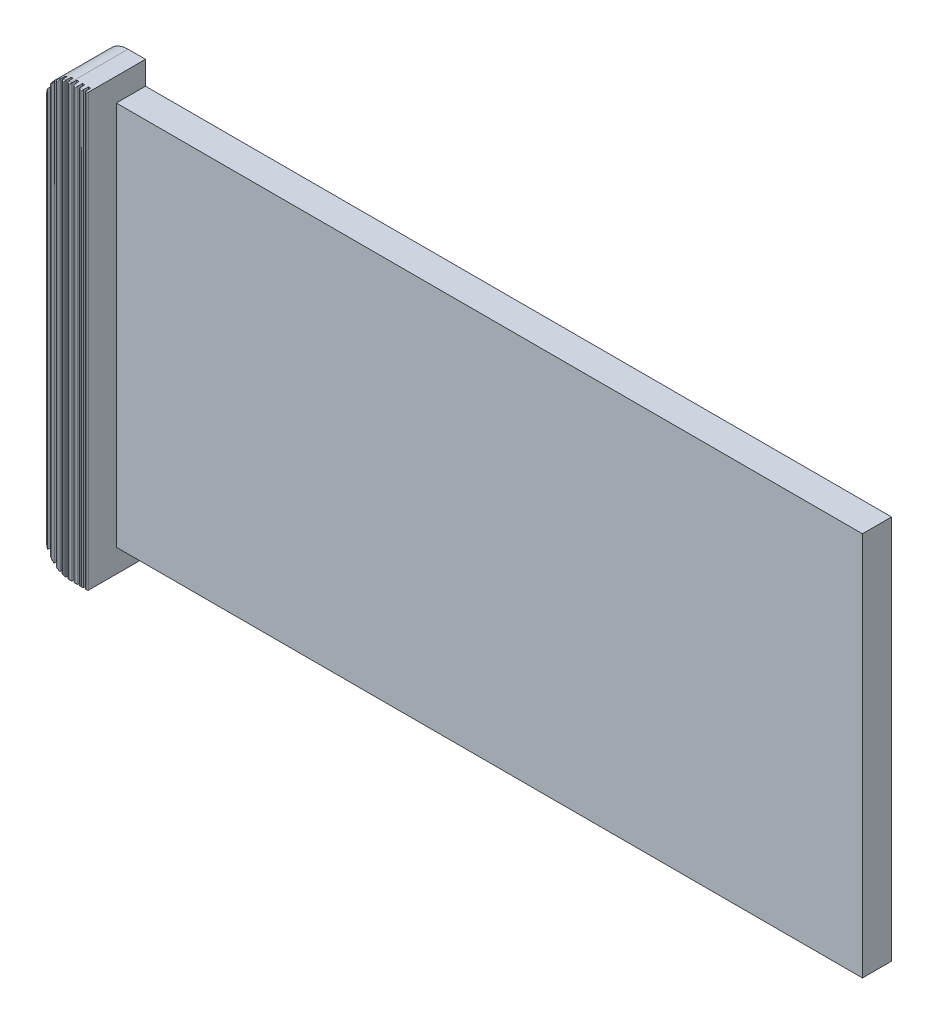
SolidWorks part; units mm, degrees
ref_plane "Alzado" through (0, 0, 0) normal (0, 0, 1) x (1, 0, 0)
ref_plane "Planta" through (0, 0, 0) normal (0, 1, 0) x (1, 0, 0)
ref_plane "Vista lateral" through (0, 0, 0) normal (1, 0, 0) x (0, 0, -1)
sketch "Croquis1" plane through (0, 0, 0) normal (0, 0, 1) x (1, 0, 0)
  line L1 (-32, 16.5) -> (32, 16.5)
  line L2 (-32, 16.5) -> (-32, -16.5)
  line L3 (-32, -16.5) -> (32, -16.5)
  line L4 (32, 16.5) -> (32, -16.5)
  line L5 (-32, 16.5) -> (32, -16.5) construction
  line L6 (-32, -16.5) -> (32, 16.5) construction
  point P0 (0, 0)
  dimension "D1" = 64
  dimension "D2" = 33
extrude "Saliente-Extruir1" add sketch "Croquis1" along normal blind 2.5
sketch "Croquis3" plane through (-32, 0, 0) normal (-1, 0, 0) x (0, 0, 1)
  line L1 (5, 18.5) -> (0, 18.5)
  line L2 (5, 18.5) -> (5, -18.5)
  line L3 (5, -18.5) -> (0, -18.5)
  line L4 (0, 18.5) -> (0, -18.5)
  point P5 (0, 0)
extrude "Saliente-Extruir2" add sketch "Croquis3" along normal blind 3.5
fillet "Redondeo1" radius 2 2 edges at (-35.5, -18.5, 2.5) (-35.5, 18.5, 2.5)
sketch "Croquis4" plane through (0, 0, 5) normal (0, 0, 1) x (1, 0, 0)
  line L1 (-32.4, 18.5) -> (-32.2, 18.5)
  line L2 (-32.4, 18.5) -> (-32.4, -18.5)
  line L3 (-32.4, -18.5) -> (-32.2, -18.5)
  line L4 (-32.2, 18.5) -> (-32.2, -18.5)
  line L5 (-33.5, 18.5) -> (-32, 18.5) construction
  line L6 (-32, 16.5) -> (-32, -16.5) construction
  line L7 (-32.9, 18.5) -> (-32.7, 18.5)
  line L8 (-32.9, 18.5) -> (-32.9, -18.5)
  line L9 (-32.9, -18.5) -> (-32.7, -18.5)
  line L10 (-32.7, 18.5) -> (-32.7, -18.5)
  line L11 (-33.4, 18.5) -> (-33.2, 18.5)
  line L12 (-33.4, 18.5) -> (-33.4, -18.5)
  line L13 (-33.4, -18.5) -> (-33.2, -18.5)
  line L14 (-33.2, 18.5) -> (-33.2, -18.5)
  line L15 (-33.9, 18.5) -> (-33.7, 18.5)
  line L16 (-33.9, 18.5) -> (-33.9, -18.5)
  line L17 (-33.9, -18.5) -> (-33.7, -18.5)
  line L18 (-33.7, 18.5) -> (-33.7, -18.5)
  line L19 (-34.4, 18.5) -> (-34.2, 18.5)
  line L20 (-34.4, 18.5) -> (-34.4, -18.5)
  line L21 (-34.4, -18.5) -> (-34.2, -18.5)
  line L22 (-34.2, 18.5) -> (-34.2, -18.5)
  line L23 (-34.9, 18.5) -> (-34.7, 18.5)
  line L24 (-34.9, 18.5) -> (-34.9, -18.5)
  line L25 (-34.9, -18.5) -> (-34.7, -18.5)
  line L26 (-34.7, 18.5) -> (-34.7, -18.5)
  line L27 (-35.4, 18.5) -> (-35.2, 18.5)
  line L28 (-35.4, 18.5) -> (-35.4, -18.5)
  line L29 (-35.4, -18.5) -> (-35.2, -18.5)
  line L30 (-35.2, 18.5) -> (-35.2, -18.5)
  dimension "D1" = 0.2
  dimension "D2" = 0.2
  dimension "D4" = 0.3
  dimension "D3" = 7
extrude "Cortar-Extruir1" cut sketch "Croquis4" against normal blind 0.5
fillet "Redondeo2" radius 0.1 30 edges at (-35.2, 0, 5) (-35.0613, 17.75, 5) (-34.9, 0, 5) (-35.0613, -17.75, 5) (-34.7, 0, 5) (-34.5541, 18.1997, 5) (-34.4, 0, 5) (-34.5541, -18.1997, 5) (-34.2, 0, 5) (-34.0517, 18.4224, 5) (-33.9, 0, 5) (-34.0517, -18.4224, 5) (-33.6001, -18.4975, 5) (-33.7, 0, 5) (-33.6001, 18.4975, 5) (-33.45, 18.5, 5) (-33.4, 0, 5) (-33.45, -18.5, 5) (-33.2, 0, 5) (-33.05, 18.5, 5) (-32.9, 0, 5) (-33.05, -18.5, 5) (-32.7, 0, 5) (-32.55, 18.5, 5) (-32.4, 0, 5) (-32.55, -18.5, 5) (-32, 0, 5) (-32.1, -18.5, 5) (-32.2, 0, 5) (-32.1, 18.5, 5)
